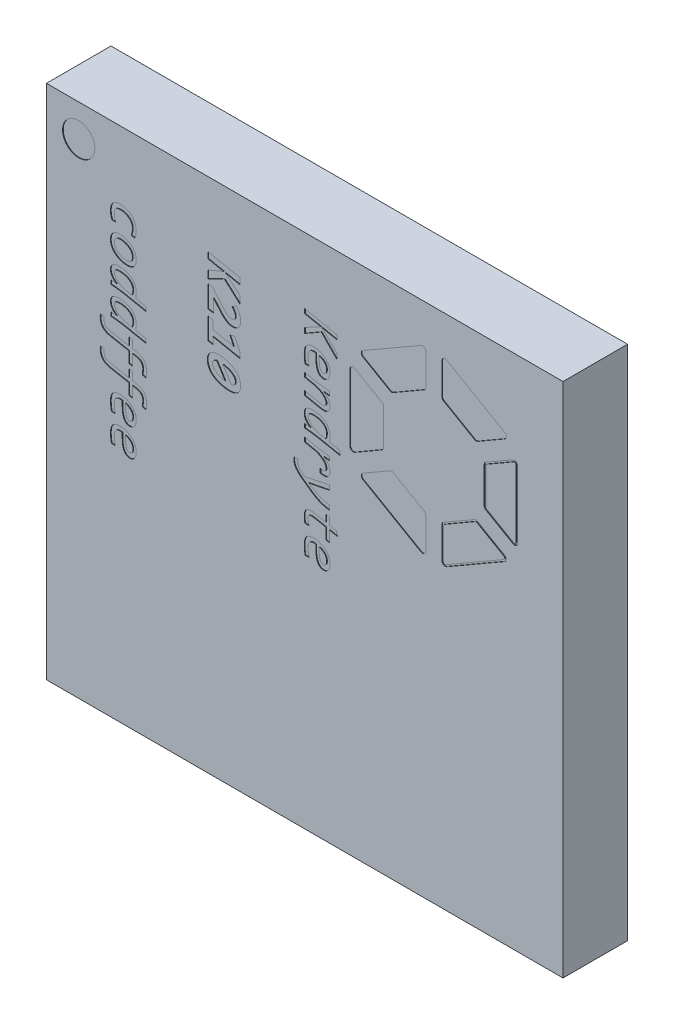
SolidWorks part; units mm, degrees
material "1023 碳钢板 (SS)"
ref_plane "前视基准面" through (0, 0, 0) normal (0, 0, 1) x (1, 0, 0)
ref_plane "上视基准面" through (0, 0, 0) normal (0, 1, 0) x (1, 0, 0)
ref_plane "右视基准面" through (0, 0, 0) normal (1, 0, 0) x (0, 0, -1)
ref_plane "芯片基底面" through (0, 0, 0.15) normal (0, 0, 1) x (1, 0, 0)
sketch "草图1" plane through (0, 0, 0.15) normal (0, 0, 1) x (1, 0, 0)
  line L1 (-4, 4) -> (4, 4)
  line L2 (-4, 4) -> (-4, -4)
  line L3 (-4, -4) -> (4, -4)
  line L4 (4, 4) -> (4, -4)
  line L5 (-4, 4) -> (4, -4) construction
  line L6 (-4, -4) -> (4, 4) construction
  point P0 (0, 0)
extrude "凸台-拉伸1" add sketch "草图1" along normal blind 1
sketch "草图2" plane through (0, 0, 0.15) normal (0, 0, -1) x (-1, 0, 0)
  line L2 (-3.575, 3.725) -> (-3.575, 3.425)
  arc A0 (-3.575, 3.725) -> (-3.575, 3.425) centre (-3.575, 3.575) ccw
revolve "旋转1" add sketch "草图2" angle 180 about L2 reverse direction yes
pattern_linear "阵列(线性)1" count 12 spacing 0.65 along (-1, 0, 0) of "旋转1"
pattern_linear "阵列(线性)2" count 12 spacing 0.65 along (0, -1, 0) of "旋转1", "阵列(线性)1"
sketch "草图3" plane through (0, 0, 1.15) normal (0, 0, 1) x (1, 0, 0)
  line L1 (0, 3) -> (0, -3) construction
  line L3 (3.0865, 1.1562) -> (2.1875, 0.6371)
  line L4 (3.0865, 1.1995) -> (2.6669, 1.4417)
  line L41 (3.299, 2.5191) -> (3.299, 1.4809)
  line L42 (3.224, 1.4376) -> (2.8044, 1.6799)
  line L43 (2.7794, 2.2768) -> (2.7794, 1.7232)
  line L44 (3.224, 2.5624) -> (2.8044, 2.3201)
  line L45 (3.099, 1.1345) -> (2.2, 0.6155)
  line L46 (2.125, 0.6588) -> (2.125, 1.1433)
  line L47 (2.6294, 1.4634) -> (2.15, 1.1866)
  line L48 (3.099, 1.2211) -> (2.6794, 1.4634)
  line L49 (1.8, 0.6155) -> (0.901, 1.1345)
  line L50 (0.901, 1.2211) -> (1.3206, 1.4634)
  line L51 (1.85, 1.1866) -> (1.3706, 1.4634)
  line L52 (1.875, 0.6588) -> (1.875, 1.1433)
  line L53 (0.701, 1.4809) -> (0.701, 2.5191)
  line L54 (0.776, 2.5624) -> (1.1956, 2.3201)
  line L55 (1.2206, 1.7232) -> (1.2206, 2.2768)
  line L56 (0.776, 1.4376) -> (1.1956, 1.6799)
  line L57 (0.901, 2.8655) -> (1.8, 3.3845)
  line L58 (1.875, 3.3412) -> (1.875, 2.8567)
  line L59 (1.3706, 2.5366) -> (1.85, 2.8134)
  line L60 (0.901, 2.7789) -> (1.3206, 2.5366)
  line L61 (2.125, 3.3412) -> (2.125, 2.8567)
  line L62 (2.2, 3.3845) -> (3.099, 2.8655)
  line L63 (2.15, 2.8134) -> (2.6294, 2.5366)
  line L64 (3.099, 2.7789) -> (2.6794, 2.5366)
  line L65 (2.6419, 1.4417) -> (2.1625, 1.165)
  line L66 (2.15, 0.6588) -> (2.15, 1.1433)
  line L67 (-1.5, 3) -> (-1.5, 0) construction
  line L68 (-3, 3) -> (-3, -3) construction
  line L69 (3.274, 2.5191) -> (3.274, 1.4809)
  line L70 (3.2365, 2.5407) -> (2.8169, 2.2984)
  line L71 (2.8044, 2.2768) -> (2.8044, 1.7232)
  line L72 (3.2365, 1.4593) -> (2.8169, 1.7016)
  arc A30 (3.224, 1.4376) -> (3.299, 1.4809) centre (3.249, 1.4809) ccw
  arc A31 (2.7794, 1.7232) -> (2.8044, 1.6799) centre (2.8294, 1.7232) ccw
  arc A32 (2.8044, 2.3201) -> (2.7794, 2.2768) centre (2.8294, 2.2768) ccw
  arc A33 (3.224, 2.5624) -> (3.299, 2.5191) centre (3.249, 2.5191) cw
  arc A34 (2.125, 0.6588) -> (2.2, 0.6155) centre (2.175, 0.6588) ccw
  arc A35 (2.15, 1.1866) -> (2.125, 1.1433) centre (2.175, 1.1433) ccw
  arc A36 (2.6794, 1.4634) -> (2.6294, 1.4634) centre (2.6544, 1.4201) ccw
  arc A37 (3.099, 1.2211) -> (3.099, 1.1345) centre (3.074, 1.1778) cw
  arc A38 (0.901, 1.2211) -> (0.901, 1.1345) centre (0.926, 1.1778) ccw
  arc A39 (1.3706, 1.4634) -> (1.3206, 1.4634) centre (1.3456, 1.4201) ccw
  arc A40 (1.875, 1.1433) -> (1.85, 1.1866) centre (1.825, 1.1433) ccw
  arc A41 (1.875, 0.6588) -> (1.8, 0.6155) centre (1.825, 0.6588) cw
  arc A42 (0.776, 2.5624) -> (0.701, 2.5191) centre (0.751, 2.5191) ccw
  arc A43 (1.2206, 2.2768) -> (1.1956, 2.3201) centre (1.1706, 2.2768) ccw
  arc A44 (1.1956, 1.6799) -> (1.2206, 1.7232) centre (1.1706, 1.7232) ccw
  arc A45 (0.776, 1.4376) -> (0.701, 1.4809) centre (0.751, 1.4809) cw
  arc A46 (1.875, 3.3412) -> (1.8, 3.3845) centre (1.825, 3.3412) ccw
  arc A47 (1.85, 2.8134) -> (1.875, 2.8567) centre (1.825, 2.8567) ccw
  arc A48 (1.3206, 2.5366) -> (1.3706, 2.5366) centre (1.3456, 2.5799) ccw
  arc A49 (0.901, 2.7789) -> (0.901, 2.8655) centre (0.926, 2.8222) cw
  arc A50 (2.125, 3.3412) -> (2.2, 3.3845) centre (2.175, 3.3412) cw
  arc A51 (3.099, 2.7789) -> (3.099, 2.8655) centre (3.074, 2.8222) ccw
  arc A52 (2.6294, 2.5366) -> (2.6794, 2.5366) centre (2.6544, 2.5799) ccw
  arc A53 (2.125, 2.8567) -> (2.15, 2.8134) centre (2.175, 2.8567) ccw
  circle A54 centre (-3.5, 3.5) radius 0.25
  arc A55 (2.15, 0.6588) -> (2.1875, 0.6371) centre (2.175, 0.6588) ccw
  arc A56 (3.0865, 1.1995) -> (3.0865, 1.1562) centre (3.074, 1.1778) cw
  arc A57 (2.6669, 1.4417) -> (2.6419, 1.4417) centre (2.6544, 1.4201) ccw
  arc A58 (2.1625, 1.165) -> (2.15, 1.1433) centre (2.175, 1.1433) ccw
  arc A59 (3.2365, 1.4593) -> (3.274, 1.4809) centre (3.249, 1.4809) ccw
  arc A60 (3.2365, 2.5407) -> (3.274, 2.5191) centre (3.249, 2.5191) cw
  arc A61 (2.8169, 2.2984) -> (2.8044, 2.2768) centre (2.8294, 2.2768) ccw
  arc A62 (2.8044, 1.7232) -> (2.8169, 1.7016) centre (2.8294, 1.7232) ccw
  text T0 "<i>Kendryte</i>" font "Consolas" height 0.5
  text T1 "<b><i>K210</i></b>" font "Consolas" height 0.5
  text T2 "<i>coddffee</i>" font "Consolas" height 0.5
  point P3 (0, 0)
  point P151 (2, 2)
  dimension "D1" = 0.025
  dimension "D2" = 0.025
extrude "切除-拉伸1" cut sketch "草图3" against normal blind 0.01
